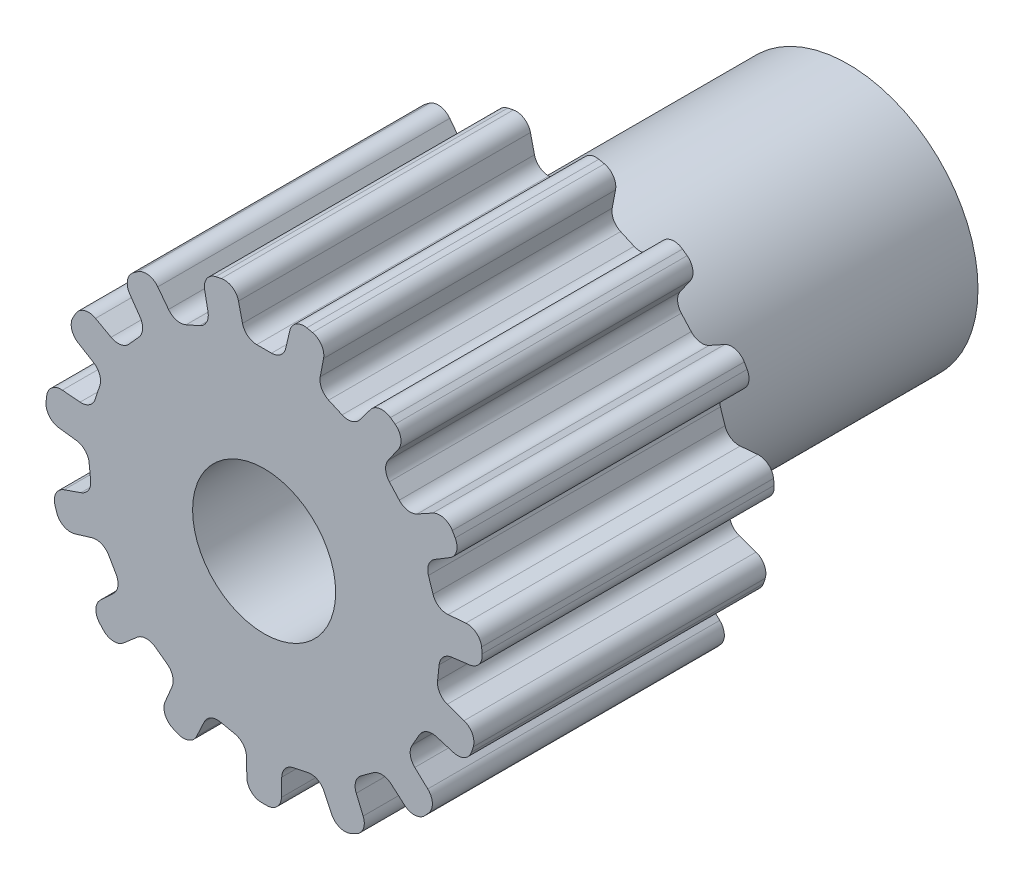
SolidWorks part; units mm, degrees
ref_plane "Front Plane" through (0, 0, 0) normal (0, 0, 1) x (1, 0, 0)
ref_plane "Top Plane" through (0, 0, 0) normal (0, 1, 0) x (1, 0, 0)
ref_plane "Right Plane" through (0, 0, 0) normal (1, 0, 0) x (0, 0, -1)
sketch "Sketch1" plane through (0, 0, 0) normal (0, 0, 1) x (1, 0, 0)
  line L0 (0, 10.6054) -> (0, -11.8313) construction
  line L1 (-9.5209, 0) -> (11.9909, 0) construction
  circle A0 centre (0, 0) radius 7.5
  circle A1 centre (0, 0) radius 2.45
  dimension "D1" = 15
  dimension "D2" = 4.9
extrude "Boss-Extrude1" add sketch "Sketch1" along normal blind 10
sketch "Sketch2" plane through (0, 0, 0) normal (0, 0, -1) x (-1, 0, 0)
  line L0 (0, 7.5) -> (0, -7.5) construction
  line L1 (-7.5, 0) -> (7.5, 0) construction
  line L2 (-0.65, 6) -> (0.65, 6)
  line L3 (-0.65, 6) -> (-1, 7.5)
  line L4 (-1, 7.5) -> (1, 7.5)
  line L5 (1, 7.5) -> (0.65, 6)
  line L6 (0, 6) -> (0, 9.2795) construction
  circle A0 centre (0, 0) radius 7.5 construction
  point P13 (0, 7.5)
  dimension "D1" = 2
  dimension "D2" = 1.3
  dimension "D3" = 0
  dimension "D4" = 1.5
extrude "Cut-Extrude1" cut sketch "Sketch2" against normal blind 10
fillet "Fillet1" radius 0.5 4 edges at (-0.9848, 7.4351, 5) (-0.65, 6, 5) (0.65, 6, 5) (0.9848, 7.4351, 5)
ref_axis "Axis1" through (0, 0, 10) along (0, 0, -1)
pattern_circular "CirPattern1" count 15 over 360 about axis through (0, 0, 10) along (0, 0, -1) of "Cut-Extrude1", "Fillet1"
sketch "Sketch3" plane through (0, 0, 0) normal (0, 0, -1) x (-1, 0, 0)
  circle A0 centre (0, 0) radius 2.45 construction
  circle A1 centre (0, 0) radius 2.45
  circle A2 centre (0, 0) radius 4.45
  dimension "D1" = 2
extrude "Boss-Extrude2" add sketch "Sketch3" along normal blind 10
